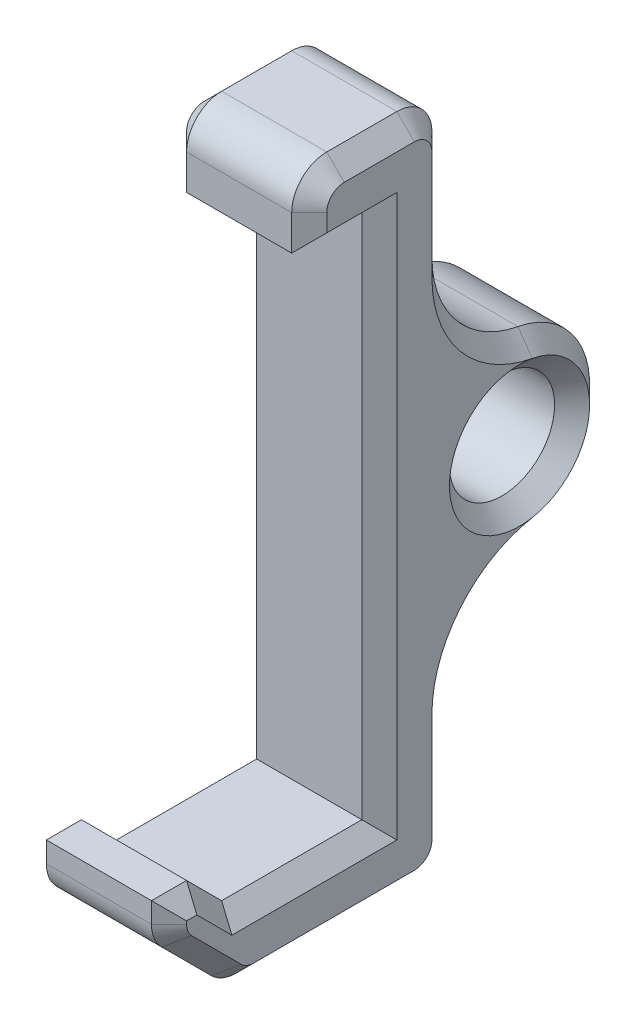
SolidWorks part; units mm, degrees
ref_plane "Front Plane" through (0, 0, 0) normal (0, 0, 1) x (1, 0, 0)
ref_plane "Top Plane" through (0, 0, 0) normal (0, 1, 0) x (1, 0, 0)
ref_plane "Right Plane" through (0, 0, 0) normal (1, 0, 0) x (0, 0, -1)
sketch "Sketch2" plane through (0, 0, 0) normal (1, 0, 0) x (0, 0, -1)
  line L0 (0, 7.5) -> (0, -7.5)
  line L1 (0, -7.5) -> (-4, -7.5)
  line L2 (-4, -7.5) -> (-5, -6.5)
  line L3 (-5, -6.5) -> (-6, -6.5)
  line L4 (-6, -6.5) -> (-6, -7.5)
  line L5 (-6, -7.5) -> (-4, -9.5)
  line L6 (-4, -9.5) -> (2, -9.5)
  line L7 (2, -9.5) -> (2, -2.5)
  line L8 (2, -2.5) -> (4, -2.5)
  line L9 (4, 2.5) -> (2, 2.5)
  line L10 (2, 2.5) -> (2, 9.5)
  line L11 (2, 9.5) -> (-2, 9.5)
  line L12 (-2, 9.5) -> (-2, 7.5)
  line L13 (-2, 7.5) -> (0, 7.5)
  arc A0 (4, 2.5) -> (4, -2.5) centre (4, 0) cw
  circle A1 centre (4, 0) radius 1.5
  point P18 (0, 0)
  dimension "D10" = 3
  dimension "D1" = 15
  dimension "D2" = 2
  dimension "D3" = 2
  dimension "D4" = 4
  dimension "D5" = 1
  dimension "D6" = 2
  dimension "D7" = 5
  dimension "D8" = 2
  dimension "D9" = 2
  dimension "D11" = 1
  dimension "D12" = 135
extrude "Boss-Extrude1" add sketch "Sketch2" along normal blind 2 and the other way blind 2 contours A0 L9 L10 L11 L12 L13 L0 L1 L2 L3 L4 L5 L6 L7 L8 A1 region at (0, -0.9195, -0.7886)
fillet "Fillet1" radius 3 2 edges at (0, 2.5, -2) (0, -2.5, -2)
fillet "Fillet2" radius 1 5 edges at (0, 9.5, 2) (0, -7.5, 6) (0, -9.5, 4) (0, -9.5, -2) (0, 9.5, -2)
chamfer "Chamfer1" distance 0.5 angle 45 42 edges at (-2, 7.5, 1) (-2, 0, 0) (-2, -7.5, 2) (-2, -7, 4.5) (-2, -6.5, 5.5) (-2, -6.7929, 6) (-2, -7.4685, 5.9239) (-2, -8.5, 5) (-2, -9.4239, 3.9685) (-2, -9.5, 1.2929) (-2, -9.2071, -1.7071) (-2, -6.9542, -2) (-2, -3.4895, -2.6939) (-2, 0, -6.5) (-2, 3.4895, -2.6939) (-2, 6.9542, -2) (-2, 9.2071, -1.7071) (-2, 9.5, 0) (-2, 9.2071, 1.7071) (-2, 8, 2) (-2, 0, -5.5) (2, 9.2071, -1.7071) (2, 6.9542, -2) (2, 3.4895, -2.6939) (2, 0, -6.5) (2, -3.4895, -2.6939) (2, -6.9542, -2) (2, -9.2071, -1.7071) (2, -9.5, 1.2929) (2, -9.4239, 3.9685) (2, -8.5, 5) (2, -7.4685, 5.9239) (2, -6.7929, 6) (2, -6.5, 5.5) (2, -7, 4.5) (2, -7.5, 2) (2, 0, 0) (2, 7.5, 1) (2, 8, 2) (2, 9.2071, 1.7071) (2, 9.5, 0) (2, 0, -5.5)
